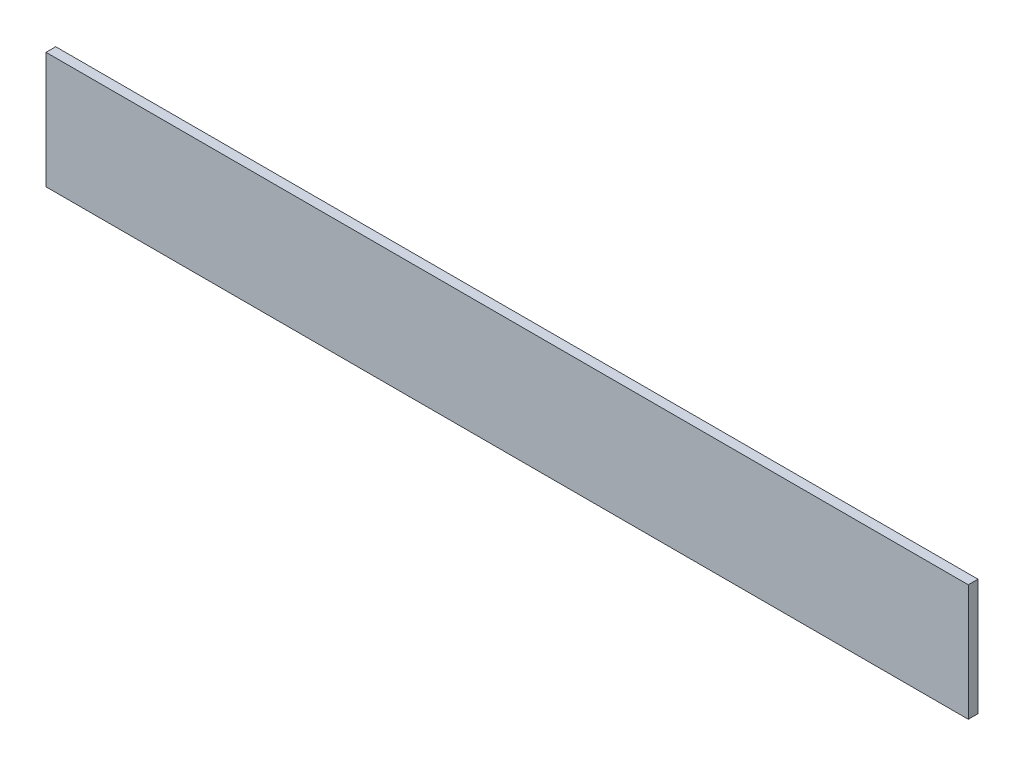
SolidWorks part; units mm, degrees
ref_plane "Plan de face" through (0, 0, 0) normal (0, 0, 1) x (1, 0, 0)
ref_plane "Plan de dessus" through (0, 0, 0) normal (0, 1, 0) x (1, 0, 0)
ref_plane "Plan de droite" through (0, 0, 0) normal (1, 0, 0) x (0, 0, -1)
sketch "Esquisse1" plane through (0, 0, 0) normal (0, 0, 1) x (1, 0, 0)
  line L1 (-142.6668, 70.5537) -> (237.3332, 70.5537)
  line L2 (-142.6668, 70.5537) -> (-142.6668, 22.5537)
  line L3 (-142.6668, 22.5537) -> (237.3332, 22.5537)
  line L4 (237.3332, 70.5537) -> (237.3332, 22.5537)
  dimension "D1" = 380
  dimension "D2" = 48
extrude "Boss.-Extru.1" add sketch "Esquisse1" along normal blind 4
